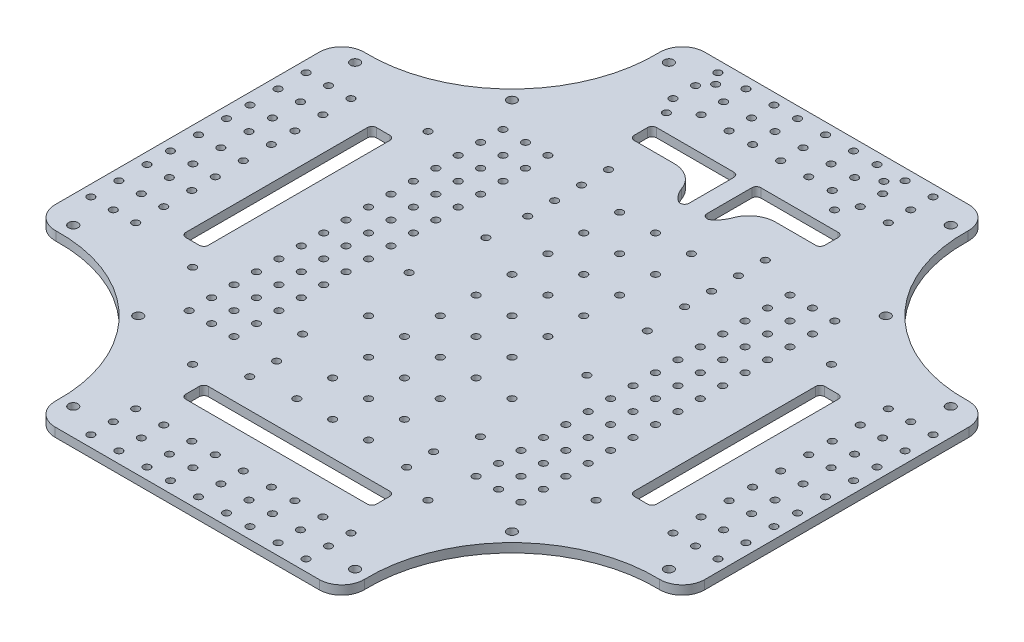
SolidWorks part; units mm, degrees
ref_plane "前视基准面" through (0, 0, 0) normal (0, 0, 1) x (1, 0, 0)
ref_plane "上视基准面" through (0, 0, 0) normal (0, 1, 0) x (1, 0, 0)
ref_plane "右视基准面" through (0, 0, 0) normal (1, 0, 0) x (0, 0, -1)
sketch "草图1" plane through (0, 0, 0) normal (0, 1, 0) x (1, 0, 0)
  line L0 (-50, 0) -> (50, 0) construction
  line L1 (0, -50) -> (0, 50) construction
  line L2 (-132.8649, -132.8649) -> (71.0003, 71.0003) construction
  line L3 (132.8649, -132.8649) -> (-71.0003, 71.0003) construction
  line L4 (-132.8649, -132.8649) -> (-132.8649, -62.8649) construction
  line L5 (-144.8649, 70) -> (-144.8649, -70)
  line L6 (70, 144.8649) -> (-70, 144.8649)
  line L7 (144.8649, -70) -> (144.8649, 70)
  line L8 (-70, -144.8649) -> (70, -144.8649)
  line L9 (-35.5, -110.0509) -> (-35.5, -264.5846) construction
  circle A0 centre (-132.8649, -62.8649) radius 2.075
  circle A1 centre (-62.8649, -132.8649) radius 2.075
  circle A2 centre (-83.3675, -83.3675) radius 2.075
  circle A3 centre (-62.8649, 132.8649) radius 2.075
  circle A4 centre (-83.3675, 83.3675) radius 2.075
  circle A5 centre (-132.8649, 62.8649) radius 2.075
  circle A6 centre (132.8649, 62.8649) radius 2.075
  circle A7 centre (83.3675, 83.3675) radius 2.075
  circle A8 centre (62.8649, 132.8649) radius 2.075
  circle A9 centre (62.8649, -132.8649) radius 2.075
  circle A10 centre (83.3675, -83.3675) radius 2.075
  circle A11 centre (132.8649, -62.8649) radius 2.075
  circle A12 centre (-132.8649, -132.8649) radius 64
  circle A13 centre (-132.8649, 132.8649) radius 64
  circle A14 centre (132.8649, 132.8649) radius 64
  circle A15 centre (132.8649, -132.8649) radius 64
  circle A16 centre (-12.5, -139.8649) radius 1.6
  circle A17 centre (12.5, -139.8649) radius 1.6
  circle A18 centre (-48, -139.8649) radius 1.6
  circle A19 centre (-23, -139.8649) radius 1.6
  circle A20 centre (23, -139.8649) radius 1.6
  circle A21 centre (48, -139.8649) radius 1.6
  circle A22 centre (-139.8649, 48) radius 1.6
  circle A23 centre (-139.8649, 23) radius 1.6
  circle A24 centre (-139.8649, 12.5) radius 1.6
  circle A25 centre (-139.8649, -12.5) radius 1.6
  circle A26 centre (-139.8649, -23) radius 1.6
  circle A27 centre (-139.8649, -48) radius 1.6
  circle A28 centre (48, 139.8649) radius 1.6
  circle A29 centre (23, 139.8649) radius 1.6
  circle A30 centre (12.5, 139.8649) radius 1.6
  circle A31 centre (-12.5, 139.8649) radius 1.6
  circle A32 centre (-23, 139.8649) radius 1.6
  circle A33 centre (-48, 139.8649) radius 1.6
  circle A34 centre (139.8649, -48) radius 1.6
  circle A35 centre (139.8649, -23) radius 1.6
  circle A36 centre (139.8649, -12.5) radius 1.6
  circle A37 centre (139.8649, 12.5) radius 1.6
  circle A38 centre (139.8649, 23) radius 1.6
  circle A39 centre (139.8649, 48) radius 1.6
  circle A40 centre (-35.5, -139.8649) radius 1.6
  circle A41 centre (35.5, -139.8649) radius 1.6
  circle A42 centre (-139.8649, -35.5) radius 1.6
  circle A43 centre (-139.8649, 35.5) radius 1.6
  circle A44 centre (-35.5, 139.8649) radius 1.6
  circle A45 centre (35.5, 139.8649) radius 1.6
  circle A46 centre (139.8649, 35.5) radius 1.6
  circle A47 centre (139.8649, -35.5) radius 1.6
  circle A48 centre (0, -139.8649) radius 1.6
  circle A49 centre (-12.5, -129.8649) radius 1.6
  circle A50 centre (12.5, -129.8649) radius 1.6
  circle A51 centre (-48, -129.8649) radius 1.6
  circle A52 centre (-23, -129.8649) radius 1.6
  circle A53 centre (23, -129.8649) radius 1.6
  circle A54 centre (48, -129.8649) radius 1.6
  circle A55 centre (-35.5, -129.8649) radius 1.6
  circle A56 centre (35.5, -129.8649) radius 1.6
  circle A57 centre (0, -129.8649) radius 1.6
  circle A58 centre (-12.5, -119.8649) radius 1.6
  circle A59 centre (12.5, -119.8649) radius 1.6
  circle A60 centre (-48, -119.8649) radius 1.6
  circle A61 centre (-23, -119.8649) radius 1.6
  circle A62 centre (23, -119.8649) radius 1.6
  circle A63 centre (48, -119.8649) radius 1.6
  circle A64 centre (-35.5, -119.8649) radius 1.6
  circle A65 centre (35.5, -119.8649) radius 1.6
  circle A66 centre (0, -119.8649) radius 1.6
  circle A67 centre (-129.8649, 12.5) radius 1.6
  circle A68 centre (-129.8649, -12.5) radius 1.6
  circle A69 centre (-129.8649, 48) radius 1.6
  circle A70 centre (-129.8649, 23) radius 1.6
  circle A71 centre (-129.8649, -23) radius 1.6
  circle A72 centre (-129.8649, -48) radius 1.6
  circle A73 centre (-129.8649, 35.5) radius 1.6
  circle A74 centre (-129.8649, -35.5) radius 1.6
  circle A75 centre (-129.8649, 0) radius 1.6
  circle A76 centre (-119.8649, 12.5) radius 1.6
  circle A77 centre (-119.8649, -12.5) radius 1.6
  circle A78 centre (-119.8649, 48) radius 1.6
  circle A79 centre (-119.8649, 23) radius 1.6
  circle A80 centre (-119.8649, -23) radius 1.6
  circle A81 centre (-119.8649, -48) radius 1.6
  circle A82 centre (-119.8649, 35.5) radius 1.6
  circle A83 centre (-119.8649, -35.5) radius 1.6
  circle A84 centre (-119.8649, 0) radius 1.6
  circle A85 centre (-139.8649, 0) radius 1.6
  circle A86 centre (12.5, 129.8649) radius 1.6
  circle A87 centre (-12.5, 129.8649) radius 1.6
  circle A88 centre (48, 129.8649) radius 1.6
  circle A89 centre (23, 129.8649) radius 1.6
  circle A90 centre (-23, 129.8649) radius 1.6
  circle A91 centre (-48, 129.8649) radius 1.6
  circle A92 centre (35.5, 129.8649) radius 1.6
  circle A93 centre (-35.5, 129.8649) radius 1.6
  circle A94 centre (0, 129.8649) radius 1.6
  circle A95 centre (12.5, 119.8649) radius 1.6
  circle A96 centre (-12.5, 119.8649) radius 1.6
  circle A97 centre (48, 119.8649) radius 1.6
  circle A98 centre (23, 119.8649) radius 1.6
  circle A99 centre (-23, 119.8649) radius 1.6
  circle A100 centre (-48, 119.8649) radius 1.6
  circle A101 centre (35.5, 119.8649) radius 1.6
  circle A102 centre (-35.5, 119.8649) radius 1.6
  circle A103 centre (0, 119.8649) radius 1.6
  circle A104 centre (0, 139.8649) radius 1.6
  circle A105 centre (129.8649, -12.5) radius 1.6
  circle A106 centre (129.8649, 12.5) radius 1.6
  circle A107 centre (129.8649, -48) radius 1.6
  circle A108 centre (129.8649, -23) radius 1.6
  circle A109 centre (129.8649, 23) radius 1.6
  circle A110 centre (129.8649, 48) radius 1.6
  circle A111 centre (129.8649, -35.5) radius 1.6
  circle A112 centre (129.8649, 35.5) radius 1.6
  circle A113 centre (129.8649, 0) radius 1.6
  circle A114 centre (119.8649, -12.5) radius 1.6
  circle A115 centre (119.8649, 12.5) radius 1.6
  circle A116 centre (119.8649, -48) radius 1.6
  circle A117 centre (119.8649, -23) radius 1.6
  circle A118 centre (119.8649, 23) radius 1.6
  circle A119 centre (119.8649, 48) radius 1.6
  circle A120 centre (119.8649, -35.5) radius 1.6
  circle A121 centre (119.8649, 35.5) radius 1.6
  circle A122 centre (119.8649, 0) radius 1.6
  circle A123 centre (139.8649, 0) radius 1.6
  point P36 (0, 0)
  point P44 (0, 0)
  point P53 (0, 0)
  point P102 (0, 0)
  point P121 (0, 0)
  point P274 (0, 0)
  dimension "D2" = 4.15
  dimension "D4" = 70
  dimension "D5" = 4
  dimension "D6" = 128
  dimension "D7" = 4
  dimension "D11" = 3.2
  dimension "D15" = 25
  dimension "D17" = 4
  dimension "D19" = 4
  dimension "D18" = 71
  dimension "D1" = 45
  dimension "D3" = 70
  dimension "D8" = 4
  dimension "D9" = 12
  dimension "D10" = 140
  dimension "D12" = 25
  dimension "D13" = 5
  dimension "D14" = 25
  dimension "D16" = 23
  dimension "D20" = 3
  dimension "D21" = 10
  dimension "D23" = 12.5
  dimension "D24" = 12.5
  dimension "D25" = 10.5
  dimension "D26" = 12.5
  dimension "D27" = 12.5
  dimension "D28" = 10.5
  dimension "D29" = 12.5
  dimension "D30" = 12.5
  dimension "D31" = 265.7299
  dimension "D22" = 4
extrude "凸台-拉伸1" add sketch "草图1" along normal mid plane 4 contours A15 L7 A14 L6 A13 L5 A12 L8 A11 A10 A9 A5 A4 A3 A2 A0 A1 A6 A7 A8 region at (0, 0, 0)
fillet "圆角1" radius 10 8 edges at (-144.8649, 0, -70) (-70, 0, -144.8649) (70, 0, -144.8649) (144.8649, 0, -70) (144.8649, 0, 70) (70, 0, 144.8649) (-144.8649, 0, 70) (-70, 0, 144.8649)
sketch "草图2" plane through (0, 2, 0) normal (0, 1, 0) x (1, 0, 0)
  line L0 (-50, 0) -> (50, 0) construction
  line L1 (0, -50) -> (0, 50) construction
  circle A0 centre (-52.5, -90) radius 1.6
  circle A1 centre (52.5, -90) radius 1.6
  circle A2 centre (-90, 52.5) radius 1.6
  circle A3 centre (-90, -52.5) radius 1.6
  circle A6 centre (90, -52.5) radius 1.6
  circle A7 centre (90, 52.5) radius 1.6
  circle A8 centre (-52.5, 90) radius 1.6 [skipped]
  circle A9 centre (52.5, 90) radius 1.6 [skipped]
  point P24 (0, 0)
  dimension "D3" = 3.2
  dimension "D1" = 105
  dimension "D2" = 90
  dimension "D4" = 4
extrude "切除-拉伸1" cut sketch "草图2" against normal through all
sketch "草图3" plane through (0, 2, 0) normal (0, 1, 0) x (1, 0, 0)
  line L0 (16.5, 134.8649) -> (16.5, 112.8649) construction
  line L5 (-44, 134.8649) -> (31, 134.8649) construction
  line L7 (-44, 134.8649) -> (-44, 112.8649) construction
  line L8 (-44, 112.8649) -> (31, 112.8649) construction
  line L9 (31, 134.8649) -> (31, 112.8649) construction
  line L10 (-11.5, 134.8649) -> (-11.5, 112.8649) construction
  circle A10 centre (-44, 134.8649) radius 1.6
  circle A11 centre (-44, 112.8649) radius 1.6
  circle A12 centre (31, 134.8649) radius 1.6
  circle A13 centre (31, 112.8649) radius 1.6
  circle A14 centre (12.5, 129.8649) radius 1.6 construction
  circle A15 centre (12.5, 139.8649) radius 1.6 construction
  dimension "D5" = 22
  dimension "D3" = 28
  dimension "D1" = 3.2
  dimension "D6" = 44
  dimension "D2" = 32.5
  dimension "D4" = 14.5
extrude "切除-拉伸2" cut sketch "草图3" against normal through all
sketch "草图4" plane through (0, 2, 0) normal (0, 1, 0) x (1, 0, 0)
  line L0 (0, 0) -> (0, -30) construction
  line L1 (-39.6345, -53.749) -> (39.6345, -53.749) construction
  line L2 (-39.6345, -53.749) -> (-39.6345, -6.251) construction
  line L3 (-39.6345, -6.251) -> (39.6345, -6.251) construction
  line L4 (39.6345, -53.749) -> (39.6345, -6.251) construction
  line L5 (-39.6345, -53.749) -> (39.6345, -6.251) construction
  line L6 (-39.6345, -6.251) -> (39.6345, -53.749) construction
  line L7 (0, 0) -> (0, -38) construction
  line L8 (0, -38) -> (-36, 24.3538) construction
  circle A0 centre (-39.6345, -6.251) radius 1.6
  circle A1 centre (-39.6345, -53.749) radius 1.6
  circle A2 centre (39.6345, -6.251) radius 1.6
  circle A3 centre (39.6345, -53.749) radius 1.6
  circle A4 centre (-36, 24.3538) radius 1.6
  circle A5 centre (36, 24.3538) radius 1.6
  point P0 (0, -30)
  dimension "D3" = 3.2
  dimension "D8" = 3.2
  dimension "D1" = 79.269
  dimension "D2" = 47.498
  dimension "D4" = 30
  dimension "D5" = 38
  dimension "D6" = 30
  dimension "D7" = 72
extrude "切除-拉伸3" cut sketch "草图4" against normal through all
sketch "草图6" plane through (0, 2, 0) normal (0, 1, 0) x (1, 0, 0)
  line L0 (0, 0) -> (0, 100) construction
  line L1 (105, 40.5) -> (105, -40.5)
  line L2 (-40.5, 105) -> (40.5, 105)
  line L3 (-42.5, 103) -> (-42.5, 97)
  line L4 (-40.5, 95) -> (40.5, 95)
  line L5 (42.5, 103) -> (42.5, 97)
  line L6 (-42.5, 105) -> (42.5, 95) construction
  line L7 (-42.5, 95) -> (42.5, 105) construction
  line L8 (103, 42.5) -> (97, 42.5)
  line L9 (95, 40.5) -> (95, -40.5)
  line L10 (103, -42.5) -> (97, -42.5)
  line L11 (105, 42.5) -> (95, -42.5) construction
  line L12 (95, 42.5) -> (105, -42.5) construction
  line L13 (40.5, -105) -> (-40.5, -105)
  line L14 (42.5, -103) -> (42.5, -97)
  line L15 (40.5, -95) -> (-40.5, -95)
  line L16 (-42.5, -103) -> (-42.5, -97)
  line L17 (42.5, -105) -> (-42.5, -95) construction
  line L18 (42.5, -95) -> (-42.5, -105) construction
  line L19 (-105, -40.5) -> (-105, 40.5)
  line L20 (-103, -42.5) -> (-97, -42.5)
  line L21 (-95, -40.5) -> (-95, 40.5)
  line L22 (-103, 42.5) -> (-97, 42.5)
  line L23 (-105, -42.5) -> (-95, 42.5) construction
  line L24 (-95, -42.5) -> (-105, 42.5) construction
  line L25 (-4, 105) -> (-4, 79.6863)
  line L26 (4, 105) -> (4, 79.6863)
  arc A0 (40.5, 105) -> (42.5, 103) centre (40.5, 103) cw
  arc A1 (-42.5, 97) -> (-40.5, 95) centre (-40.5, 97) ccw
  arc A2 (-40.5, 105) -> (-42.5, 103) centre (-40.5, 103) ccw
  arc A3 (40.5, 95) -> (42.5, 97) centre (40.5, 97) ccw
  arc A4 (105, -40.5) -> (103, -42.5) centre (103, -40.5) cw
  arc A5 (97, 42.5) -> (95, 40.5) centre (97, 40.5) ccw
  arc A6 (105, 40.5) -> (103, 42.5) centre (103, 40.5) ccw
  arc A7 (95, -40.5) -> (97, -42.5) centre (97, -40.5) ccw
  arc A8 (-40.5, -105) -> (-42.5, -103) centre (-40.5, -103) cw
  arc A9 (42.5, -97) -> (40.5, -95) centre (40.5, -97) ccw
  arc A10 (40.5, -105) -> (42.5, -103) centre (40.5, -103) ccw
  arc A11 (-40.5, -95) -> (-42.5, -97) centre (-40.5, -97) ccw
  arc A12 (-105, 40.5) -> (-103, 42.5) centre (-103, 40.5) cw
  arc A13 (-97, -42.5) -> (-95, -40.5) centre (-97, -40.5) ccw
  arc A14 (-105, -40.5) -> (-103, -42.5) centre (-103, -40.5) ccw
  arc A15 (-95, 40.5) -> (-97, 42.5) centre (-97, 40.5) ccw
  arc A16 (-11.3137, 87) -> (11.3137, 87) centre (0, 91) ccw
  arc A17 (-11.3137, 87) -> (-22.6274, 95) centre (-22.6274, 83) ccw
  arc A18 (11.3137, 87) -> (22.6274, 95) centre (22.6274, 83) cw
  point P70 (0, 0)
  dimension "D4" = 2
  dimension "D6" = 12
  dimension "D7" = 12
  dimension "D1" = 85
  dimension "D2" = 10
  dimension "D3" = 100
  dimension "D8" = 4
  dimension "D9" = 8
  dimension "D5" = 4
extrude "切除-拉伸4" cut sketch "草图6" against normal through all contours L21 A15 L22 A12 L19 A14 L20 A13 | L9 A7 L10 A4 L1 A6 L8 A5 | L15 A11 L16 A8 L13 A10 L14 A9 | L2 A2 L3 A1 L4 L25 | A17 A16 L25 L4 | A16 A18 L4 L26 | L4 A3 L5 A0 L2 L26 region at (100, 2, 0) region at (-23.1658, 2, -100) region at (23.1658, 2, -100) region at (-8.7057, 2, -89.3711) region at (8.7057, 2, -89.3711) region at (0, 2, 100) region at (-100, 2, 0)
fillet "圆角2" radius 2 4 edges at (4, 0, -79.6863) (-4, 0, -79.6863) (4, 0, -105) (-4, 0, -105)
sketch "草图7" plane through (0, -2, 0) normal (0, -1, 0) x (1, 0, 0)
  line L0 (0, 0) -> (26.4146, 0) construction
  line L1 (0, 0) -> (0, 24.9353) construction
  circle A0 centre (-16, 0) radius 1.6
  circle A1 centre (0, 16) radius 1.6
  circle A2 centre (16, 0) radius 1.6
  circle A3 centre (0, -16) radius 1.6
  circle A4 centre (0, 32) radius 1.6
  circle A5 centre (0, 48) radius 1.6
  circle A6 centre (0, 64) radius 1.6
  circle A7 centre (0, 80) radius 1.6
  circle A8 centre (0, 0) radius 1.6
  circle A10 centre (0, -64) radius 1.6
  circle A11 centre (0, -48) radius 1.6
  circle A12 centre (0, -32) radius 1.6
  circle A13 centre (16, 16) radius 1.6
  circle A14 centre (16, 32) radius 1.6
  circle A15 centre (16, 48) radius 1.6
  circle A16 centre (16, 64) radius 1.6
  circle A17 centre (16, 80) radius 1.6
  circle A18 centre (16, -16) radius 1.6
  circle A19 centre (16, -64) radius 1.6
  circle A20 centre (16, -48) radius 1.6
  circle A21 centre (16, -32) radius 1.6
  circle A22 centre (-16, 16) radius 1.6
  circle A23 centre (-16, 32) radius 1.6
  circle A24 centre (-16, 48) radius 1.6
  circle A25 centre (-16, 64) radius 1.6
  circle A26 centre (-16, 80) radius 1.6
  circle A27 centre (-16, -16) radius 1.6
  circle A28 centre (-16, -64) radius 1.6
  circle A29 centre (-16, -48) radius 1.6
  circle A30 centre (-16, -32) radius 1.6
  circle A31 centre (-64, 0) radius 1.6
  circle A32 centre (-54, 0) radius 1.6
  circle A33 centre (-74, 0) radius 1.6
  circle A34 centre (-64, -10) radius 1.6
  circle A35 centre (-54, -10) radius 1.6
  circle A36 centre (-74, -10) radius 1.6
  circle A37 centre (-64, -20) radius 1.6
  circle A38 centre (-54, -20) radius 1.6
  circle A39 centre (-74, -20) radius 1.6
  circle A40 centre (-64, -30) radius 1.6
  circle A41 centre (-54, -30) radius 1.6
  circle A42 centre (-74, -30) radius 1.6
  circle A43 centre (-64, -40) radius 1.6
  circle A44 centre (-54, -40) radius 1.6
  circle A45 centre (-74, -40) radius 1.6
  circle A46 centre (-64, -50) radius 1.6
  circle A47 centre (-54, -50) radius 1.6
  circle A48 centre (-74, -50) radius 1.6
  circle A49 centre (-64, -60) radius 1.6
  circle A50 centre (-54, -60) radius 1.6
  circle A51 centre (-74, -60) radius 1.6
  circle A52 centre (-64, -70) radius 1.6
  circle A53 centre (-54, -70) radius 1.6
  circle A54 centre (-74, -70) radius 1.6
  circle A55 centre (-74, 70) radius 1.6
  circle A56 centre (-54, 70) radius 1.6
  circle A57 centre (-64, 70) radius 1.6
  circle A58 centre (-74, 60) radius 1.6
  circle A59 centre (-54, 60) radius 1.6
  circle A60 centre (-64, 60) radius 1.6
  circle A61 centre (-74, 50) radius 1.6
  circle A62 centre (-54, 50) radius 1.6
  circle A63 centre (-64, 50) radius 1.6
  circle A64 centre (-74, 40) radius 1.6
  circle A65 centre (-54, 40) radius 1.6
  circle A66 centre (-64, 40) radius 1.6
  circle A67 centre (-74, 30) radius 1.6
  circle A68 centre (-54, 30) radius 1.6
  circle A69 centre (-64, 30) radius 1.6
  circle A70 centre (-74, 20) radius 1.6
  circle A71 centre (-54, 20) radius 1.6
  circle A72 centre (-64, 20) radius 1.6
  circle A73 centre (-74, 10) radius 1.6
  circle A74 centre (-54, 10) radius 1.6
  circle A75 centre (-64, 10) radius 1.6
  circle A76 centre (64, 10) radius 1.6
  circle A77 centre (54, 10) radius 1.6
  circle A78 centre (74, 10) radius 1.6
  circle A79 centre (64, 20) radius 1.6
  circle A80 centre (54, 20) radius 1.6
  circle A81 centre (74, 20) radius 1.6
  circle A82 centre (64, 30) radius 1.6
  circle A83 centre (54, 30) radius 1.6
  circle A84 centre (74, 30) radius 1.6
  circle A85 centre (64, 40) radius 1.6
  circle A86 centre (54, 40) radius 1.6
  circle A87 centre (74, 40) radius 1.6
  circle A88 centre (64, 50) radius 1.6
  circle A89 centre (54, 50) radius 1.6
  circle A90 centre (74, 50) radius 1.6
  circle A91 centre (64, 60) radius 1.6
  circle A92 centre (54, 60) radius 1.6
  circle A93 centre (74, 60) radius 1.6
  circle A94 centre (64, 70) radius 1.6
  circle A95 centre (54, 70) radius 1.6
  circle A96 centre (74, 70) radius 1.6
  circle A97 centre (74, -70) radius 1.6
  circle A98 centre (54, -70) radius 1.6
  circle A99 centre (64, -70) radius 1.6
  circle A100 centre (74, -60) radius 1.6
  circle A101 centre (54, -60) radius 1.6
  circle A102 centre (64, -60) radius 1.6
  circle A103 centre (74, -50) radius 1.6
  circle A104 centre (54, -50) radius 1.6
  circle A105 centre (64, -50) radius 1.6
  circle A106 centre (74, -40) radius 1.6
  circle A107 centre (54, -40) radius 1.6
  circle A108 centre (64, -40) radius 1.6
  circle A109 centre (74, -30) radius 1.6
  circle A110 centre (54, -30) radius 1.6
  circle A111 centre (64, -30) radius 1.6
  circle A112 centre (74, -20) radius 1.6
  circle A113 centre (54, -20) radius 1.6
  circle A114 centre (64, -20) radius 1.6
  circle A115 centre (74, -10) radius 1.6
  circle A116 centre (54, -10) radius 1.6
  circle A117 centre (64, -10) radius 1.6
  circle A118 centre (74, 0) radius 1.6
  circle A119 centre (54, 0) radius 1.6
  circle A120 centre (64, 0) radius 1.6
  circle A121 centre (-35, 82) radius 1.6
  circle A122 centre (-35, 70) radius 1.6
  circle A123 centre (35, 70) radius 1.6
  circle A124 centre (35, 82) radius 1.6
  circle A125 centre (-35, -42) radius 1.6
  circle A126 centre (-35, -54) radius 1.6
  circle A127 centre (-35, -66) radius 1.6
  circle A128 centre (-35, -78) radius 1.6
  circle A129 centre (35, -78) radius 1.6
  circle A130 centre (35, -66) radius 1.6
  circle A131 centre (35, -54) radius 1.6
  circle A132 centre (35, -42) radius 1.6
  circle A133 centre (32, 32) radius 1.6
  circle A134 centre (-32, 32) radius 1.6
  point P12 (0, 0)
  dimension "D2" = 4
  dimension "D3" = 3.2
  dimension "D4" = 5
  dimension "D6" = 2
  dimension "D16" = 12
  dimension "D20" = 12
  dimension "D1" = 16
  dimension "D5" = 16
  dimension "D7" = 16
  dimension "D9" = 16
  dimension "D10" = 38
  dimension "D11" = 10
  dimension "D12" = 10
  dimension "D13" = 8
  dimension "D14" = 10
  dimension "D15" = 35
  dimension "D17" = 70
  dimension "D18" = 12
  dimension "D19" = 4
  dimension "D21" = 35
  dimension "D22" = 78
  dimension "D23" = 16
  dimension "D8" = 2
extrude "切除-拉伸5" cut sketch "草图7" against normal through all and the other way through all
